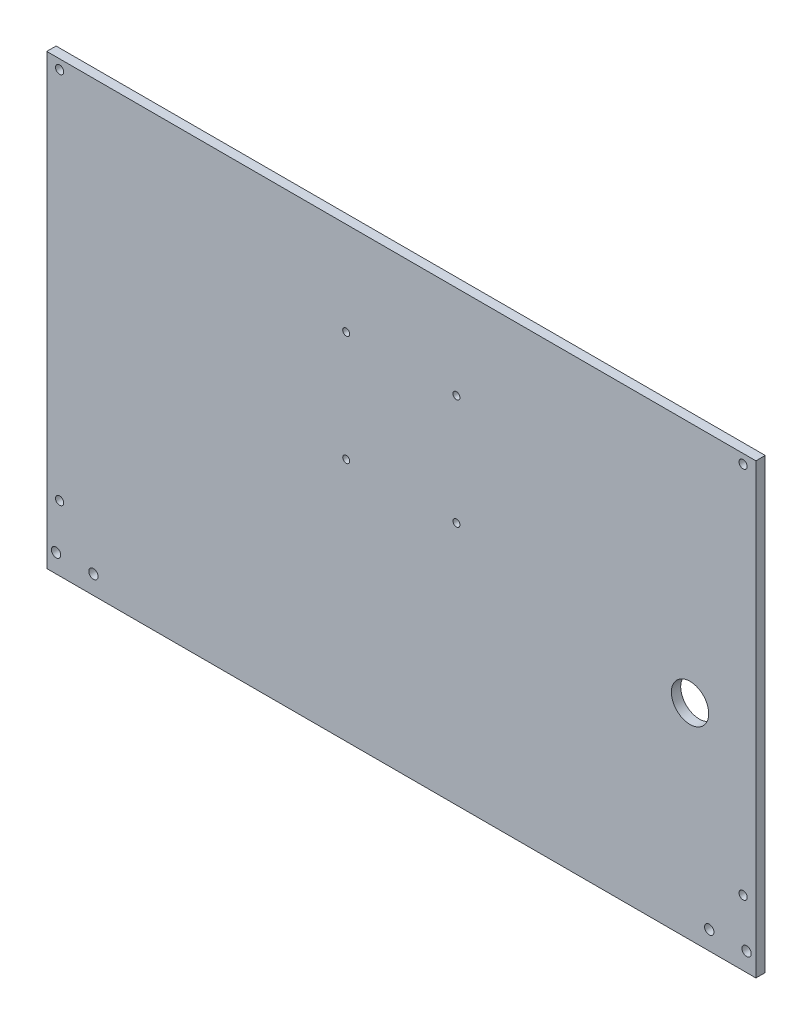
SolidWorks part; units mm, degrees
ref_plane "Front Plane" through (0, 0, 0) normal (0, 0, 1) x (1, 0, 0)
ref_plane "Top Plane" through (0, 0, 0) normal (0, 1, 0) x (1, 0, 0)
ref_plane "Right Plane" through (0, 0, 0) normal (1, 0, 0) x (0, 0, -1)
sketch "Sketch1" plane through (0, 0, 0) normal (0, 0, 1) x (1, 0, 0)
  line L1 (-241.3, -152.4) -> (241.3, -152.4)
  line L2 (-241.3, -152.4) -> (-241.3, 152.4)
  line L3 (-241.3, 152.4) -> (241.3, 152.4)
  line L4 (241.3, -152.4) -> (241.3, 152.4)
  line L5 (-241.3, -152.4) -> (241.3, 152.4) construction
  line L6 (-241.3, 152.4) -> (241.3, -152.4) construction
  point P0 (0, 0)
  dimension "D1" = 482.6
  dimension "D2" = 304.8
extrude "Boss-Extrude1" add sketch "Sketch1" along normal blind 6.35
sketch "Sketch2" plane through (0, 0, 6.35) normal (0, 0, 1) x (1, 0, 0)
  line L0 (-241.3, 0) -> (241.3, 0) construction
  line L1 (-241.3, 152.4) -> (-241.3, -152.4) construction
  line L2 (241.3, -152.4) -> (241.3, 152.4) construction
  line L3 (241.3, 152.4) -> (-241.3, 152.4) construction
  circle A0 centre (-232.5624, 146.05) radius 2.7813
  circle A1 centre (-232.5624, -107.95) radius 2.7813
  dimension "D2" = 5.5626
  dimension "D3" = 5.5626
  dimension "D1" = 8.7376
  dimension "D4" = 6.35
  dimension "D5" = 254
extrude "Cut-Extrude1" cut sketch "Sketch2" against normal through all
mirror "Mirror1" about plane through (0, 0, 0) normal (1, 0, 0) of "Cut-Extrude1"
sketch "Sketch3" plane through (0, 0, 6.35) normal (0, 0, 1) x (1, 0, 0)
  line L0 (-241.3, -139.7) -> (241.3, -139.7) construction
  line L1 (-241.3, 152.4) -> (-241.3, -152.4) construction
  line L2 (241.3, -152.4) -> (241.3, 152.4) construction
  line L3 (-241.3, -152.4) -> (241.3, -152.4) construction
  circle A0 centre (-234.95, -139.7) radius 3.175
  circle A1 centre (-209.55, -139.7) radius 3.175
  dimension "D2" = 6.35
  dimension "D3" = 6.35
  dimension "D4" = 25.4
  dimension "D5" = 6.35
  dimension "D1" = 12.7
extrude "Cut-Extrude2" cut sketch "Sketch3" against normal through all
mirror "Mirror2" about plane through (0, 0, 0) normal (1, 0, 0) of "Cut-Extrude2"
sketch "Sketch4" plane through (0, 0, 6.35) normal (0, 0, 1) x (1, 0, 0)
  line L0 (241.3, 152.4) -> (-241.3, 152.4) construction
  circle A0 centre (196.469, -12.7) radius 12.7
  dimension "D2" = 25.4
  dimension "D1" = 196.469
  dimension "D3" = 165.1
extrude "Cut-Extrude3" cut sketch "Sketch4" against normal through all
sketch "Sketch5" plane through (0, 0, 6.35) normal (0, 0, 1) x (1, 0, 0)
  line L0 (241.3, 152.4) -> (-241.3, 152.4) construction
  line L1 (-37.5, 13.9) -> (37.5, 13.9) construction
  line L2 (-37.5, 13.9) -> (-37.5, 88.9) construction
  line L3 (-37.5, 88.9) -> (37.5, 88.9) construction
  line L4 (37.5, 13.9) -> (37.5, 88.9) construction
  line L5 (-37.5, 13.9) -> (37.5, 88.9) construction
  line L6 (-37.5, 88.9) -> (37.5, 13.9) construction
  circle A0 centre (-37.5, 88.9) radius 2.3749
  circle A1 centre (37.5, 88.9) radius 2.3749
  circle A2 centre (37.5, 13.9) radius 2.3749
  circle A3 centre (-37.5, 13.9) radius 2.3749
  point P0 (0, 51.4)
  point P8 (-50.8, 51.4)
  point P9 (-50.8, 51.4)
  point P13 (0, 51.4)
  dimension "D4" = 4.7498
  dimension "D5" = 4.7498
  dimension "D6" = 4.7498
  dimension "D7" = 4.7498
  dimension "D1" = 75
  dimension "D2" = 75
  dimension "D3" = 63.5
extrude "Cut-Extrude4" cut sketch "Sketch5" against normal through all
